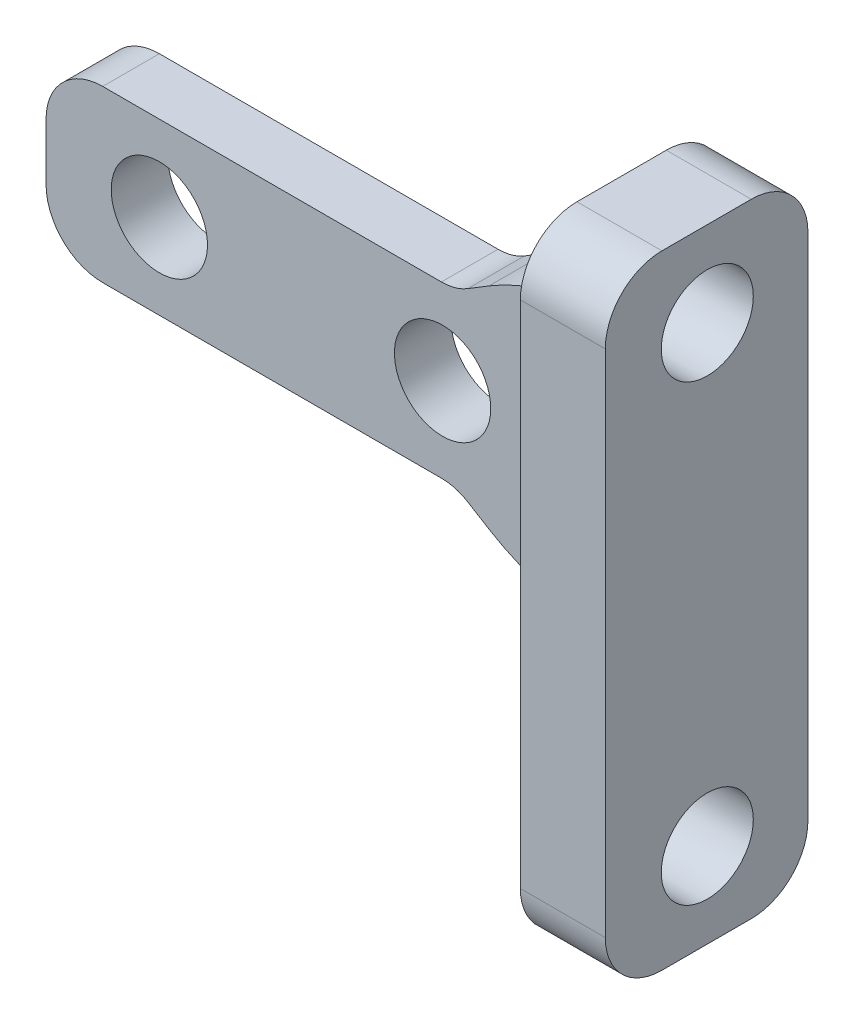
SolidWorks part; units mm, degrees
ref_plane "Front Plane" through (0, 0, 0) normal (0, 0, 1) x (1, 0, 0)
ref_plane "Top Plane" through (0, 0, 0) normal (0, 1, 0) x (1, 0, 0)
ref_plane "Right Plane" through (0, 0, 0) normal (1, 0, 0) x (0, 0, -1)
sketch "Sketch1" plane through (0, 0, 0) normal (0, 0, 1) x (1, 0, 0)
  line L0 (0, 0) -> (10, 0) construction
  line L3 (-4, 3) -> (-4, -3)
  line L4 (-4, -3) -> (9.9583, -3)
  line L7 (20.9, -11) -> (20.9, 11)
  line L10 (9.9583, 3) -> (-4, 3)
  line L11 (20.9, 11.7) -> (20.9, 0.8414) construction
  line L12 (20.9, 11) -> (17.9, 11)
  line L13 (20.9, 11) -> (20.9, -11)
  line L14 (20.9, -11) -> (17.9, -11)
  line L15 (17.9, 11) -> (17.9, -11)
  line L16 (15.5807, 4.83) -> (17.9, 4.83)
  line L17 (-5.099, 3) -> (-15, 3) construction
  line L18 (15.5807, -4.83) -> (17.9, -4.83)
  line L20 (10.8914, 3.2626) -> (11.6424, 3.7217)
  line L22 (10.8914, -3.2626) -> (11.6424, -3.7217)
  circle A2 centre (0, 0) radius 1.5 construction
  circle A3 centre (10, 0) radius 1.5 construction
  arc A4 (9.9583, 3) -> (10.8914, 3.2626) centre (9.9583, 4.7891) ccw
  arc A5 (9.9583, -3) -> (10.8914, -3.2626) centre (9.9583, -4.7891) cw
  arc A6 (11.6424, 3.7217) -> (15.5807, 4.83) centre (15.5807, -2.7214) cw
  arc A7 (11.6424, -3.7217) -> (15.5807, -4.83) centre (15.5807, 2.7214) ccw
  point P7 (-4, 0)
  point P17 (20.9, 0)
  dimension "D2" = 3
  dimension "D1" = 10
  dimension "D3" = 22
  dimension "D5" = 4
  dimension "D6" = 3
extrude "Boss-Extrude1" add sketch "Sketch1" along normal blind 2 contours L15 A4 L10 L3 L4 | L15 L7 region at (8.0458, 0, 0) region at (19.4, 0, 0)
extrude "Boss-Extrude2" add sketch "Sketch1<3>" along normal up to surface (7.154 mm away) contours L12 L15 L14 L7 region at (19.4, 0, 0)
sketch "Sketch1<3>" plane through (0, 0, 0) normal (0, 0, 1) x (1, 0, 0) same geometry as "Sketch1"
hole_wizard "M3 Clearance Hole1" positions "Sketch2" profile "Sketch4" hole size "M3" standard "ANSI Metric" end condition through all
sketch "Sketch2" plane through (0, 0, 2) normal (0, 0, 1) x (1, 0, 0)
  point P0 (0, 0)
  point P5 (10, 0)
sketch "Sketch4" plane through (0, 0, 2) normal (1, 0, 0) x (0, -1, 0)
  line L0 (0, 0) -> (0, 2)
  line L1 (0, 2) -> (1.7, 2)
  line L2 (1.7, 2) -> (1.7, 0)
  line L5 (1.7, 0) -> (0, 0)
  line L11 (0, -6.35) -> (0, 107.95) construction
  dimension "Thru Hole Dia." = 3.4
  dimension "Thru Hole Depth" = 2
fillet "Fillet1" radius 2 6 edges at (-4, 3, 1) (-4, -3, 1) (19.4, -11, 7.154) (19.4, 11, 7.154) (19.4, 11, 0) (19.4, -11, 0)
sketch "Sketch6" plane through (20.9, 0, 0) normal (1, 0, 0) x (0, 0, -1)
  line L0 (0, -11) -> (0, 11) construction
  line L1 (-3.554, 8) -> (-3.554, -8)
  line L3 (0, 11) -> (0, -11) construction
  circle A0 centre (-3.554, -8) radius 1.625
  circle A1 centre (-3.554, 8) radius 1.625
  point P5 (0, 0)
  point P11 (-3.554, 0)
  dimension "D2" = 3.25
  dimension "D3" = 3.554
  dimension "D4" = 16
extrude "Cut-Extrude1" cut sketch "Sketch6" against normal blind 7.5 contours A0 | A1 region at (20.9, -6.8835, 2.4375) region at (20.9, 9.1165, 4.6705)
fillet "Fillet2" radius 1 1 edges at (17.9, 0, 2)
sketch "Sketch7" plane through (0, 0, 0) normal (0, 1, 0) x (1, 0, 0)
  line L0 (13.4, 0) -> (19.4, -7.154)
  line L4 (20.9, -5.154) -> (20.9, -2) construction
  line L5 (9.9583, 0) -> (-4, 0) construction
  line L6 (20.9, -7.154) -> (17.9, -7.154) construction
  line L7 (20.9, -5.154) -> (20.9, -2) construction
  dimension "D1" = 1.5
  dimension "D2" = 7.5
chamfer "Chamfer1" distance 0.5 angle 45 2 edges at (17.9, -4.83, 1.5) (17.9, 4.83, 1.5)
